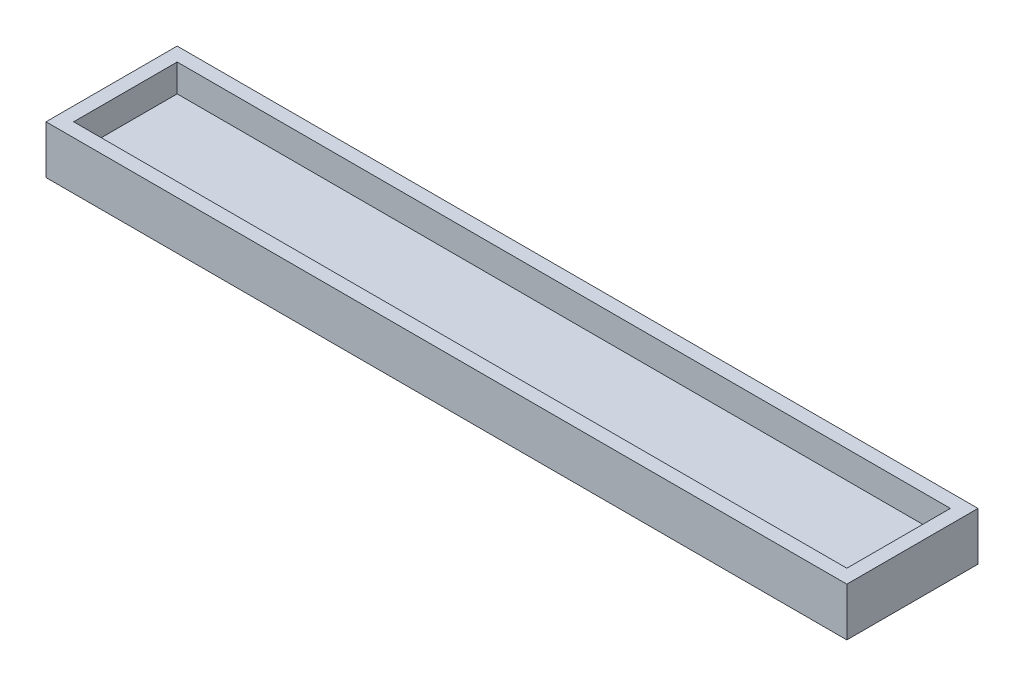
SolidWorks part; units mm, degrees
ref_plane "Front Plane" through (0, 0, 0) normal (0, 0, 1) x (1, 0, 0)
ref_plane "Top Plane" through (0, 0, 0) normal (0, 1, 0) x (1, 0, 0)
ref_plane "Right Plane" through (0, 0, 0) normal (1, 0, 0) x (0, 0, -1)
sketch "Sketch1" plane through (0, 0, 0) normal (0, 1, 0) x (1, 0, 0)
  line L0 (-2, -2) -> (114, -2)
  line L1 (0, 0) -> (112, 0)
  line L2 (0, 0) -> (0, 15)
  line L3 (0, 15) -> (112, 15)
  line L4 (112, 0) -> (112, 15)
  line L5 (114, -2) -> (114, 17)
  line L6 (-2, 17) -> (114, 17)
  line L7 (-2, -2) -> (-2, 17)
  dimension "D1" = 112
  dimension "D2" = 15
  dimension "D3" = 2
extrude "bottom" add sketch "Sketch1" along normal blind 3 contours L1 L4 L3 L2 region at (56, 0, -7.5)
extrude "raised edge" add sketch "Sketch1<3>" along normal offset from surface (7 mm away) 4 contours L7 L0 L5 L6 L4 L1 L2 L3 region at (-0.8245, 0, -7.5) up to face at (56, 3, -7.5) offset beyond the face yes
sketch "Sketch1<3>" plane through (0, 0, 0) normal (0, 1, 0) x (1, 0, 0) same geometry as "Sketch1"
